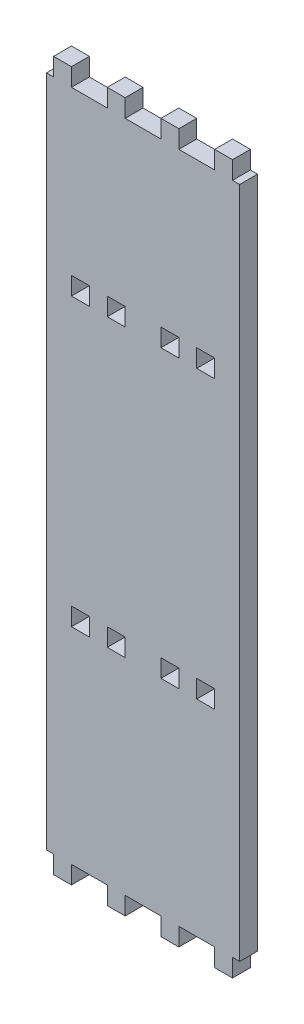
SolidWorks part; units mm, degrees
ref_plane "Plan de face" through (0, 0, 0) normal (0, 0, 1) x (1, 0, 0)
ref_plane "Plan de dessus" through (0, 0, 0) normal (0, 1, 0) x (1, 0, 0)
ref_plane "Plan de droite" through (0, 0, 0) normal (1, 0, 0) x (0, 0, -1)
sketch "Esquisse1" plane through (0, 0, 0) normal (0, 0, 1) x (1, 0, 0)
  line L0 (0, 0) -> (0, 94) construction
  line L1 (-22.1872, 94) -> (27.2472, 94) construction
  line L2 (-25, 188) -> (-27, 188)
  line L3 (-27, 188) -> (-27, 0)
  line L4 (-27, 0) -> (-25, 0)
  line L5 (-5, 0) -> (5, 0)
  line L6 (25, 0) -> (27, 0)
  line L7 (27, 0) -> (27, 188)
  line L8 (27, 188) -> (25, 188)
  line L9 (5, 188) -> (-5, 188)
  point P17 (0, 0)
  point P18 (5, 142.5)
  point P19 (-12.5, 146.9724)
  line B0 (-15, 0) -> (-15, 11.1075) construction
  line B1 (-15, 0) -> (-20, 0)
  line B2 (-20, -5) -> (-25, -5)
  line B3 (-25, -5) -> (-25, 0)
  line B4 (-20, -5) -> (-20, 0)
  line B5 (-15, 0) -> (-10, 0)
  line B6 (-10, 0) -> (-10, -5)
  line B7 (-10, -5) -> (-5, -5)
  line B8 (-5, -5) -> (-5, 0)
  line B9 (15, 0) -> (15, 11.1075) construction
  line B10 (15, 0) -> (20, 0)
  line B11 (20, -5) -> (25, -5)
  line B12 (25, -5) -> (25, 0)
  line B13 (20, -5) -> (20, 0)
  line B14 (15, 0) -> (10, 0)
  line B15 (10, 0) -> (10, -5)
  line B16 (10, -5) -> (5, -5)
  line B17 (5, -5) -> (5, 0)
  line B18 (15, 188) -> (15, 176.8925) construction
  line B19 (15, 188) -> (20, 188)
  line B20 (20, 193) -> (25, 193)
  line B21 (25, 193) -> (25, 188)
  line B22 (20, 193) -> (20, 188)
  line B23 (15, 188) -> (10, 188)
  line B24 (10, 188) -> (10, 193)
  line B25 (10, 193) -> (5, 193)
  line B26 (5, 193) -> (5, 188)
  line B27 (-15, 188) -> (-15, 176.8925) construction
  line B28 (-15, 188) -> (-20, 188)
  line B29 (-20, 193) -> (-25, 193)
  line B30 (-25, 193) -> (-25, 188)
  line B31 (-20, 193) -> (-20, 188)
  line B32 (-15, 188) -> (-10, 188)
  line B33 (-10, 188) -> (-10, 193)
  line B34 (-10, 193) -> (-5, 193)
  line B35 (-5, 193) -> (-5, 188)
  line B36 (10, 60) -> (15, 60) construction
  line B37 (10, 62.5) -> (5, 62.5)
  line B38 (10, 62.5) -> (10, 57.5)
  line B39 (10, 57.5) -> (5, 57.5)
  line B40 (5, 62.5) -> (5, 57.5)
  line B41 (15, 62.5) -> (20, 62.5)
  line B42 (15, 62.5) -> (15, 57.5)
  line B43 (15, 57.5) -> (20, 57.5)
  line B44 (20, 62.5) -> (20, 57.5)
  line B45 (12.5, 60) -> (12.5, 66.9724) construction
  circle B46 centre (12.5, 60) radius 2 construction
  line B47 (-15, 60) -> (-10, 60) construction
  line B48 (-15, 62.5) -> (-20, 62.5)
  line B49 (-15, 62.5) -> (-15, 57.5)
  line B50 (-15, 57.5) -> (-20, 57.5)
  line B51 (-20, 62.5) -> (-20, 57.5)
  line B52 (-10, 62.5) -> (-5, 62.5)
  line B53 (-10, 62.5) -> (-10, 57.5)
  line B54 (-10, 57.5) -> (-5, 57.5)
  line B55 (-5, 62.5) -> (-5, 57.5)
  line B56 (-12.5, 60) -> (-12.5, 66.9724) construction
  circle B57 centre (-12.5, 60) radius 2 construction
  line B58 (-15, 140) -> (-10, 140) construction
  line B59 (-15, 142.5) -> (-20, 142.5)
  line B60 (-15, 142.5) -> (-15, 137.5)
  line B61 (-15, 137.5) -> (-20, 137.5)
  line B62 (-20, 142.5) -> (-20, 137.5)
  line B63 (-10, 142.5) -> (-5, 142.5)
  line B64 (-10, 142.5) -> (-10, 137.5)
  line B65 (-10, 137.5) -> (-5, 137.5)
  line B66 (-5, 142.5) -> (-5, 137.5)
  line B67 (-12.5, 140) -> (-12.5, 146.9724) construction
  circle B68 centre (-12.5, 140) radius 2 construction
  line B69 (10, 140) -> (15, 140) construction
  line B70 (10, 142.5) -> (5, 142.5)
  line B71 (10, 142.5) -> (10, 137.5)
  line B72 (10, 137.5) -> (5, 137.5)
  line B73 (5, 142.5) -> (5, 137.5)
  line B74 (15, 142.5) -> (20, 142.5)
  line B75 (15, 142.5) -> (15, 137.5)
  line B76 (15, 137.5) -> (20, 137.5)
  line B77 (20, 142.5) -> (20, 137.5)
  line B78 (12.5, 140) -> (12.5, 146.9724) construction
  circle B79 centre (12.5, 140) radius 2 construction
  dimension "D1" = 30
  dimension "D2" = 2
  dimension "D3" = 2
  dimension "D4" = 188
  dimension "D5" = 80
  dimension "D6" = 60
sketch_block_instance "Insert M3 plots ep 5mm-1"
sketch_block "Insert M3 plots ep 5mm" parameters "D1"=10, "D2"=5, "D3"=5
sketch_block_instance "Insert M3 plots ep 5mm-3"
sketch_block_instance "Insert M3 plots ep 5mm-4"
sketch_block_instance "Insert M3 plots ep 5mm-5"
sketch_block_instance "Trou M4 plots 5mm-1"
sketch_block "Trou M4 plots 5mm" parameters "D2"=4, "D5"=4, "D1"=5, "D3"=5, "D4"=5
sketch_block_instance "Trou M4 plots 5mm-2"
sketch_block_instance "Trou M4 plots 5mm-3"
sketch_block_instance "Trou M4 plots 5mm-4"
extrude "Boss.-Extru.1" add sketch "Esquisse1" along normal blind 5 contours B35 B34 B33 B32 B28 B31 B29 B30 L2 L3 L4 B3 B2 B4 B1 B5 B6 B7 B8 L5 B17 B16 B15 B14 B10 B13 B11 B12 L6 L7 L8 B21 B20 B22 B19 B23 B24 B25 B26 L9 region at (0, 93.8818, 0)
